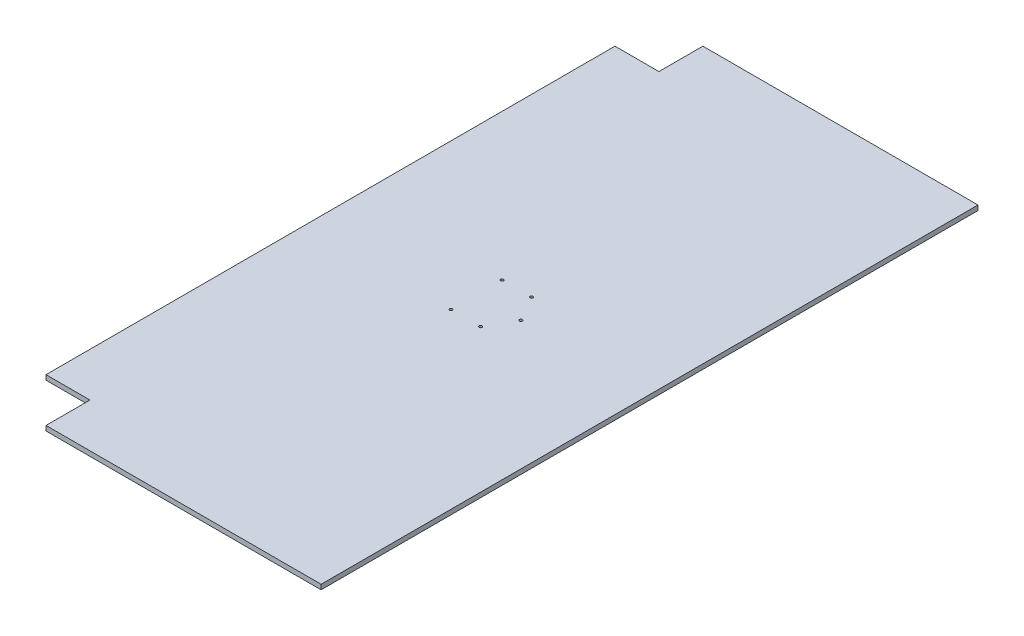
SolidWorks part; units mm, degrees
ref_plane "Front Plane" through (0, 0, 0) normal (0, 0, 1) x (1, 0, 0)
ref_plane "Top Plane" through (0, 0, 0) normal (0, 1, 0) x (1, 0, 0)
ref_plane "Right Plane" through (0, 0, 0) normal (1, 0, 0) x (0, 0, -1)
sketch "Sketch1" plane through (0, 0, 0) normal (0, 1, 0) x (1, 0, 0)
  line L5 (-304.5, -612.5) -> (304.5, -612.5)
  line L6 (-304.5, -612.5) -> (-304.5, 612.5)
  line L7 (-304.5, 612.5) -> (304.5, 612.5)
  line L14 (304.5, -612.5) -> (304.5, 612.5)
  line L15 (-304.5, -612.5) -> (304.5, 612.5) construction
  line L16 (-304.5, 612.5) -> (304.5, -612.5) construction
  line L17 (304.5, 612.5) -> (224.5, 612.5)
  line L18 (304.5, 612.5) -> (304.5, 497.5)
  line L21 (-304.5, 612.5) -> (-845.5, 612.5)
  line L22 (-304.5, 612.5) -> (-304.5, 497.5)
  line L26 (-304.5, -532.5) -> (-304.5, -612.5)
  line L27 (-304.5, -612.5) -> (-845.5, -612.5)
  line L29 (304.5, -612.5) -> (224.5, -612.5)
  line L30 (304.5, -612.5) -> (304.5, -532.5)
  point P0 (0, 0)
  dimension "D1" = 609
  dimension "D2" = 1225
extrude "Boss-Extrude1" add sketch "Sketch1" along normal blind 9 contours L6 L5 region at (0, 0, 0)
sketch "Sketch2" plane through (0, 9, 0) normal (0, 1, 0) x (1, 0, 0)
  line L0 (304.5, -612.5) -> (304.5, 612.5) construction
  line L1 (304.5, -612.5) -> (304.5, 612.5)
  line L2 (290.5, 612.5) -> (290.5, -612.5)
  line L4 (290.5, -612.5) -> (803.5, -612.5)
  line L5 (885.5, -530.5) -> (885.5, 533)
  line L6 (803.5, 612.5) -> (290.5, 612.5)
  line L7 (803.5, -612.5) -> (803.5, -530.5)
  line L8 (290.5, -612.5) -> (803.5, -612.5)
  line L9 (885.5, -530.5) -> (885.5, 533)
  line L10 (803.5, 612.5) -> (290.5, 612.5)
  line L23 (803.5, -612.5) -> (803.5, -530.5)
  line L24 (803.5, -530.5) -> (885.5, -530.5)
  line L25 (803.5, -530.5) -> (885.5, -530.5)
  line L26 (885.5, 533) -> (803.5, 533)
  line L27 (885.5, 533) -> (803.5, 533)
  line L28 (803.5, 533) -> (803.5, 612.5)
  line L29 (803.5, 533) -> (803.5, 612.5)
  line L30 (290.5, 612.5) -> (290.5, -612.5)
  line L31 (290.5, 612.5) -> (290.5, -612.5)
  line M5 (-304.5, -612.5) -> (304.5, -612.5)
  line M6 (304.5, -612.5) -> (304.5, 612.5)
  line M7 (304.5, 612.5) -> (-304.5, 612.5)
  dimension "D1" = 0
extrude "Cut-Extrude1" cut sketch "Sketch2" against normal blind 10 contours L2 M7 M5 M6 region at (297.5, 9, 0)
sketch "Sketch3" plane through (0, 9, 0) normal (0, 1, 0) x (1, 0, 0)
  line L7 (-304.5, 612.5) -> (-222.5, 612.5)
  line L8 (-304.5, 612.5) -> (-304.5, 530.5)
  line L9 (-304.5, 530.5) -> (-222.5, 530.5)
  line L10 (-222.5, 612.5) -> (-222.5, 530.5)
  line L12 (-304.5, -612.5) -> (-222.5, -612.5)
  line L13 (-304.5, -612.5) -> (-304.5, -530.5)
  line L14 (-304.5, -530.5) -> (-222.5, -530.5)
  line L15 (-222.5, -612.5) -> (-222.5, -530.5)
  dimension "D1" = 82
  dimension "D2" = 82
  dimension "D3" = 82
  dimension "D4" = 82
extrude "Cut-Extrude5" cut sketch "Sketch3" against normal blind 10
sketch "Sketch4" plane through (0, 9, 0) normal (0, 1, 0) x (1, 0, 0)
  circle A1 centre (23, 47.6314) radius 2.75
  circle A4 centre (-32, -47.6314) radius 2.75
  circle A5 centre (23, -47.6314) radius 2.75
  circle A7 centre (50.5, 0) radius 2.75
  circle A9 centre (-32, 47.6314) radius 2.75
extrude "Cut-Extrude6" cut sketch "Sketch4" against normal blind 10
